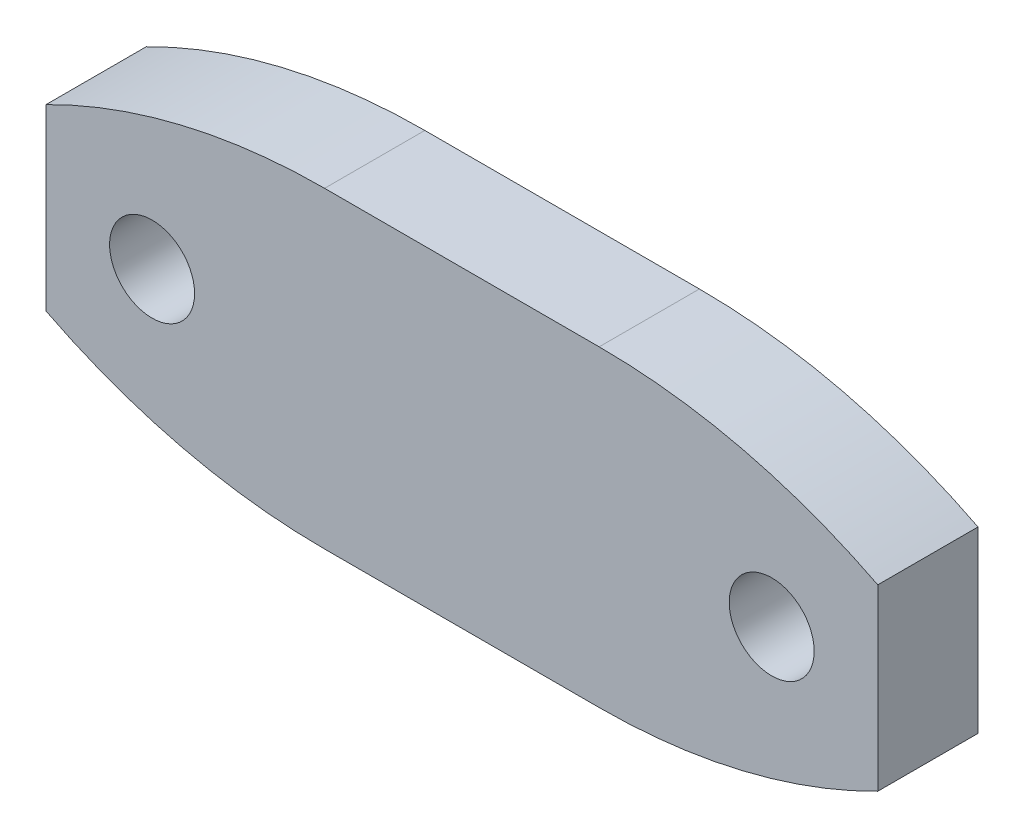
SolidWorks part; units mm, degrees
ref_plane "Front Plane" through (0, 0, 0) normal (0, 0, 1) x (1, 0, 0)
ref_plane "Top Plane" through (0, 0, 0) normal (0, 1, 0) x (1, 0, 0)
ref_plane "Right Plane" through (0, 0, 0) normal (1, 0, 0) x (0, 0, -1)
sketch "Sketch1" plane through (0, 0, 0) normal (0, 0, 1) x (1, 0, 0)
  line L1 (0, 0) -> (63.9, 0)
  line L2 (0, 0) -> (0, 24)
  line L3 (0, 24) -> (63.9, 24)
  line L4 (63.9, 0) -> (63.9, 24)
  dimension "D1" = 63.9
  dimension "D2" = 24
extrude "Boss-Extrude1" add sketch "Sketch1" along normal blind 7.7
sketch "Sketch2" plane through (0, 0, 7.7) normal (0, 0, 1) x (1, 0, 0)
  line L0 (31.95, 12) -> (55.75, 12) construction
  line L1 (31.95, 24) -> (31.95, 0) construction
  line L2 (63.9, 24) -> (0, 24) construction
  line L3 (0, 0) -> (63.9, 0) construction
  line L4 (31.95, 12) -> (8.15, 12) construction
  dimension "D1" = 47.6
hole_wizard "5/16-18 Tapped Hole1" positions "3DSketch1" profile "Sketch3" tap size "5/16-18" standard "ANSI Inch" end condition through all
sketch3d "3DSketch1"
  point P0 (8.15, 12, 7.7)
  point P3 (55.75, 12, 7.7)
sketch "Sketch3" plane through (8.15, 12, 7.7) normal (1, 0, 0) x (0, -1, 0)
  line L0 (0, 0) -> (0, 7.7)
  line L1 (0, 7.7) -> (3.2639, 7.7)
  line L2 (3.2639, 7.7) -> (3.2639, 0)
  line L5 (3.2639, 0) -> (0, 0)
  line L11 (0, -6.35) -> (0, 107.95) construction
  dimension "Thru Tap Drill Dia." = 6.5278
  dimension "Thru Tap Drill Depth" = 7.7
cosmetic thread "Hole Thread1" parameters "D2"=7.9375
cosmetic thread "Hole Thread2" parameters "D2"=7.9375
sketch "Sketch4" plane through (0, 0, 7.7) normal (0, 0, 1) x (1, 0, 0)
  line L0 (63.9, 24) -> (63.9, 18.8676)
  line L1 (0, 24) -> (0, 0) construction
  line L2 (31.95, 12) -> (8.15, 12) construction
  line L3 (31.95, 12) -> (55.75, 12) construction
  line L4 (31.95, 24) -> (31.95, 0) construction
  line L5 (31.95, 12) -> (8.15, 12) construction
  line L6 (31.95, 12) -> (55.75, 12) construction
  line L7 (31.95, 24) -> (31.95, 0) construction
  line L12 (21.4029, 24) -> (0, 24)
  line L14 (63.9, 18.8676) -> (63.9, 24)
  line L16 (0, 24) -> (0, 0)
  line L17 (0, 0) -> (63.9, 0)
  line L18 (63.9, 0) -> (63.9, 24)
  line L19 (63.9, 24) -> (0, 24)
  line L20 (0, 24) -> (0, 18.8676)
  line L24 (63.9, 24) -> (0, 24) construction
  line L25 (42.4971, 24) -> (63.9, 24)
  line L26 (42.4971, 0) -> (63.9, 0)
  line L27 (0, 0) -> (0, 5.1324)
  line L28 (63.9, 5.1324) -> (63.9, 0)
  line L29 (21.4029, 0) -> (0, 0)
  line L30 (63.9, 0) -> (63.9, 5.1324)
  arc A0 (21.4029, 24) -> (0, 18.8676) centre (21.4029, -23.1928) ccw
  arc A1 (42.4971, 24) -> (63.9, 18.8676) centre (42.4971, -23.1928) cw
  arc A2 (42.4971, 0) -> (63.9, 5.1324) centre (42.4971, 47.1928) ccw
  arc A3 (21.4029, 0) -> (0, 5.1324) centre (21.4029, 47.1928) cw
  point P3 (22.3757, 26.15)
  point P5 (0, 0)
  point P8 (22.3757, 26.15)
  point P16 (0, 0)
  point P19 (0, 0)
  point P20 (0, 0)
  point P21 (24.8471, 24)
  point P22 (0, 0)
  point P23 (21.4029, 24)
  point P34 (0, 0)
  point P35 (0, 0)
  point P36 (0, 18.8676)
  point P37 (0, 0)
  line M6 (0, 24) -> (0, 0)
  line M7 (0, 0) -> (63.9, 0)
  line M8 (63.9, 0) -> (63.9, 24)
  line M9 (63.9, 24) -> (0, 24)
  dimension "D1" = 0
extrude "Cut-Extrude1" cut sketch "Sketch4" against normal through all contours A0 M9 M6 | A3 M7 M6 | A2 M7 M8 | A1 M9 M8 region at (58.6092, 22.4758, 7.7) region at (58.6092, 1.5242, 7.7) region at (5.2908, 22.4758, 7.7) region at (5.2908, 1.5242, 7.7)
